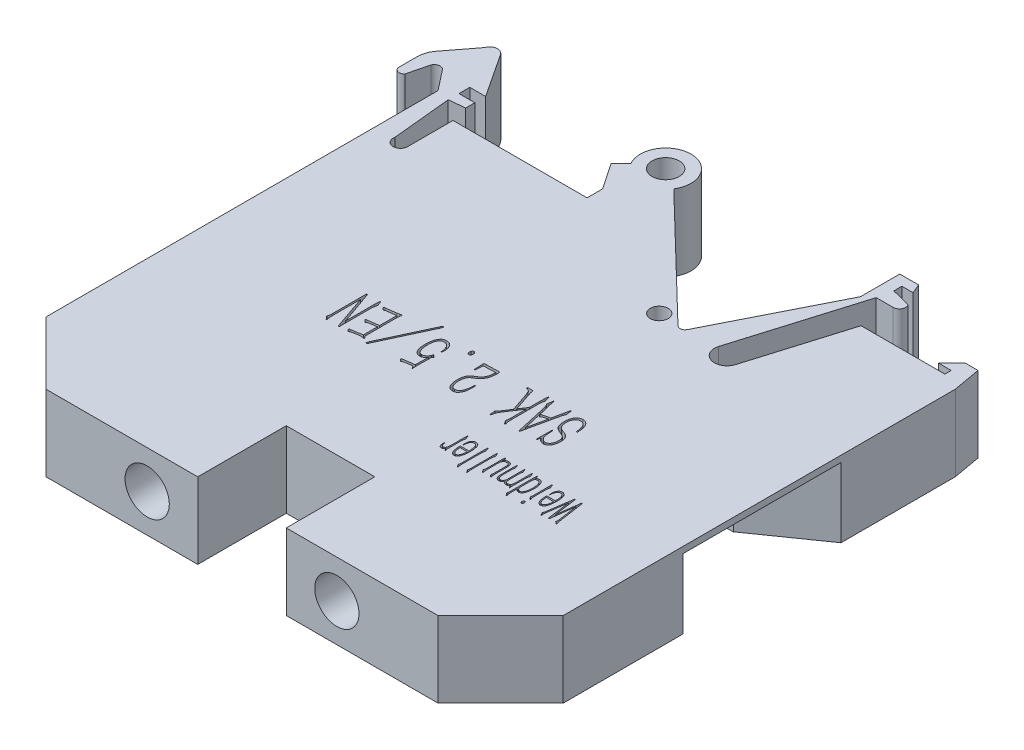
SolidWorks part; units mm, degrees
ref_plane "前视基准面" through (0, 0, 0) normal (0, 0, 1) x (1, 0, 0)
ref_plane "上视基准面" through (0, 0, 0) normal (0, 1, 0) x (1, 0, 0)
ref_plane "右视基准面" through (0, 0, 0) normal (1, 0, 0) x (0, 0, -1)
sketch "草图1" plane through (0, 0, 0) normal (0, 1, 0) x (1, 0, 0)
  line L0 (-61.5074, 0) -> (61.1732, 0) construction
  line L1 (0, 0) -> (0, 95.9382) construction
  line L2 (-3.5, 7) -> (3.5, 7)
  line L3 (3.5, 7) -> (3.5, 0)
  line L4 (3.5, 0) -> (15.5, 0)
  line L5 (15.5, 0) -> (20.4497, 4.9497)
  line L6 (20.4497, 4.9497) -> (20.4497, 35.9497)
  line L7 (-20.4497, 4.9497) -> (-20.4497, 35.9497)
  line L8 (-15.5, 0) -> (-20.4497, 4.9497)
  line L9 (-3.5, 0) -> (-15.5, 0)
  line L10 (-3.5, 7) -> (-3.5, 0)
  line L11 (20.4497, 35.9497) -> (20.0647, 38.1333)
  line L12 (20.0647, 38.1333) -> (19.0647, 38.1333)
  line L13 (19.0647, 38.1333) -> (18.0041, 37.0726)
  line L14 (18.0041, 37.0726) -> (19.0041, 37.0726)
  line L15 (19.0041, 37.0726) -> (19.0041, 36.5726)
  line L16 (-18.9543, 31.0334) -> (-19.4188, 35.7245)
  line L17 (12.3799, 36.5726) -> (10.0805, 28.9455)
  line L18 (8.1656, 29.5227) -> (11.052, 39.0971)
  line L19 (11.052, 39.0971) -> (12.3896, 39.0971)
  line L20 (12.8059, 39.874) -> (11.2867, 40.2529)
  line L21 (11.2867, 40.2529) -> (11.2867, 40.8921)
  line L22 (11.2867, 40.8921) -> (12.1702, 40.8921)
  line L23 (12.1702, 40.8921) -> (11.8608, 41.6446)
  line L24 (11.8608, 41.6446) -> (10.3682, 41.6446)
  line L25 (10.3682, 41.6446) -> (10.3682, 38.5389)
  line L26 (10.3682, 38.5389) -> (5.7821, 29.4476)
  line L27 (5.1289, 29.344) -> (-4.3994, 38.5389)
  line L28 (-7.833, 38.5907) -> (-8.6206, 37.803)
  line L29 (-8.6206, 37.803) -> (-7.2128, 35.7245)
  line L30 (-7.2128, 35.7245) -> (-7.2128, 34.4978)
  line L31 (-7.2128, 34.4978) -> (-17.8128, 34.4978)
  line L32 (-17.8128, 34.4978) -> (-17.8128, 30.9126)
  line L33 (-19.4188, 35.7245) -> (-18.1635, 35.8488)
  line L34 (12.3799, 36.5726) -> (-28.4316, 36.5726) construction
  line L35 (-18.1635, 35.8488) -> (-18.1635, 36.5726)
  line L36 (-18.1635, 36.5726) -> (-19.4188, 36.5726)
  line L37 (-19.4188, 36.5726) -> (-19.4188, 37.429)
  line L38 (-19.4188, 37.429) -> (-18.1635, 37.429)
  line L39 (-18.1635, 37.429) -> (-20.4497, 40.8921)
  line L40 (-21.5551, 40.7351) -> (-23.2038, 38.5907)
  line L41 (-23.5988, 37.429) -> (-23.5988, 35.9497)
  line L42 (-22.9, 35.7733) -> (-22.4849, 37.429)
  line L43 (-21.639, 37.4666) -> (-20.4497, 35.9497)
  line L45 (19.0041, 36.5726) -> (12.3799, 36.5726)
  arc A0 (10.0805, 28.9455) -> (8.1656, 29.5227) centre (9.123, 29.2341) cw
  arc A1 (12.3896, 39.0971) -> (12.8059, 39.874) centre (12.3896, 39.5971) ccw
  arc A2 (5.7821, 29.4476) -> (5.1289, 29.344) centre (5.4182, 29.6311) cw
  arc A3 (-4.3994, 38.5389) -> (-7.833, 38.5907) centre (-6.1005, 39.6013) ccw
  arc A4 (-17.8128, 30.9126) -> (-18.9543, 31.0334) centre (-18.3899, 30.9126) cw
  arc A5 (-20.4497, 40.8921) -> (-21.5551, 40.7351) centre (-20.9652, 40.5517) ccw
  arc A6 (-23.2038, 38.5907) -> (-23.5988, 37.429) centre (-21.6929, 37.429) ccw
  arc A7 (-23.5988, 35.9497) -> (-22.9, 35.7733) centre (-23.2038, 36.0421) ccw
  arc A8 (-22.4849, 37.429) -> (-21.639, 37.4666) centre (-22.0534, 37.2546) cw
  point P16 (0, 7)
  dimension "D8" = 0.5
  dimension "D9" = 0.5
  dimension "D1" = 7
  dimension "D2" = 7
  dimension "D3" = 12
  dimension "D4" = 7
  dimension "D5" = 135
  dimension "D6" = 31
  dimension "D7" = 10.6
  dimension "D10" = 1
  dimension "D11" = 1.5
  dimension "D12" = 1
extrude "凸台-拉伸1" add sketch "草图1" along normal blind 6
sketch "草图2" plane through (0, 0, 0) normal (0, 0, 1) x (1, 0, 0)
  line L0 (-3.5, 6) -> (-3.5, 0) construction
  line L1 (3.5, 6) -> (3.5, 0) construction
  circle A0 centre (-7.5, 3) radius 1.75
  circle A1 centre (7.5, 3) radius 1.75
  point P6 (-3.5, 3)
  point P7 (3.5, 3)
  dimension "D1" = 3.5
  dimension "D2" = 4
  dimension "D3" = 4
extrude "切除-拉伸1" cut sketch "草图2" against normal blind 5
sketch "草图3" plane through (0, 0, -5) normal (0, 0, 1) x (1, 0, 0)
  line L1 (-7.75, 1.5875) -> (-7.25, 1.5875)
  line L2 (-7.75, 1.5875) -> (-7.75, 4.4125)
  line L3 (-7.75, 4.4125) -> (-7.25, 4.4125)
  line L4 (-7.25, 1.5875) -> (-7.25, 4.4125)
  line L5 (-7.75, 1.5875) -> (-7.25, 4.4125) construction
  line L6 (-7.75, 4.4125) -> (-7.25, 1.5875) construction
  line L7 (7.25, 1.5875) -> (7.75, 1.5875)
  line L8 (7.25, 1.5875) -> (7.25, 4.4125)
  line L9 (7.25, 4.4125) -> (7.75, 4.4125)
  line L10 (7.75, 1.5875) -> (7.75, 4.4125)
  line L11 (7.25, 1.5875) -> (7.75, 4.4125) construction
  line L12 (7.25, 4.4125) -> (7.75, 1.5875) construction
  point P0 (-7.5, 3)
  point P6 (7.5, 3)
  dimension "D1" = 0.5
extrude "切除-拉伸2" cut sketch "草图3" against normal blind 1
sketch "草图4" plane through (0, 6, 0) normal (0, 1, 0) x (1, 0, 0)
  circle A0 centre (-6.1005, 39.6013) radius 1.0746
  arc A1 (-4.3994, 38.5389) -> (-7.833, 38.5907) centre (-6.1005, 39.6013) ccw construction
extrude "切除-拉伸3" cut sketch "草图4" against normal through all
sketch "草图5" plane through (0, 6, 0) normal (0, 1, 0) x (1, 0, 0)
  circle A0 centre (3.5586, 29.433) radius 0.7079
extrude "切除-拉伸4" cut sketch "草图5" against normal through all
sketch "草图6" plane through (-20.4497, 0, 0) normal (-1, 0, 0) x (0, 0, 1)
  line L0 (-35.9497, 0) -> (-4.9497, 0) construction
  line L1 (-26.9151, 5.5) -> (-14.4151, 5.5)
  line L2 (-26.9151, 5.5) -> (-26.9151, 0)
  line L3 (-26.9151, 0) -> (-14.4151, 0)
  line L4 (-14.4151, 5.5) -> (-14.4151, 0)
  line L5 (-26.9151, 5.5) -> (-14.4151, 0) construction
  line L6 (-26.9151, 0) -> (-14.4151, 5.5) construction
  point P0 (-20.6651, 2.75)
  dimension "D1" = 12.5
  dimension "D2" = 5.5
extrude "切除-拉伸5" cut sketch "草图6" against normal blind 5
sketch "草图7" plane through (0, 5.5, 0) normal (0, -1, 0) x (1, 0, 0)
  line L0 (-20.4497, -26.9151) -> (-15.4497, -26.9151)
  line L2 (-15.4497, -26.9151) -> (-15.4497, -23.4151)
  line L4 (-15.4497, -14.4151) -> (-15.4497, -26.9151) construction
  line L5 (-15.4497, -23.4151) -> (-20.4497, -26.9151)
  line L6 (-20.4497, -14.4151) -> (-15.4497, -14.4151)
  line L7 (-15.4497, -14.4151) -> (-15.4497, -17.9151)
  line L8 (-15.4497, -17.9151) -> (-20.4497, -14.4151)
  dimension "D1" = 3.5
  dimension "D2" = 3.5
extrude "凸台-拉伸2" add sketch "草图7" along normal up to surface (5.5 mm away) up to face at (-3.8878, 0, -30.6955)
sketch "草图8" plane through (-15.4497, 0, 0) normal (-1, 0, 0) x (0, 0, 1)
  line L0 (-17.9151, 0) -> (-17.9151, 5.5) construction
  line L1 (-23.3973, 0) -> (-17.9151, 0)
  line L2 (-23.3973, 0) -> (-23.3973, 4.6608)
  line L3 (-23.3973, 4.6608) -> (-17.9151, 4.6608)
  line L4 (-17.9151, 0) -> (-17.9151, 4.6608)
  line L5 (-23.3973, 0) -> (-17.9151, 4.6608) construction
  line L6 (-23.3973, 4.6608) -> (-17.9151, 0) construction
  point P0 (-20.6562, 2.3304)
extrude "切除-拉伸6" cut sketch "草图8" against normal blind 10
mirror "镜向1" about plane through (0, 0, 0) normal (1, 0, 0) of "切除-拉伸5", "凸台-拉伸2", "切除-拉伸6"
sketch "草图9" plane through (0, 6, 0) normal (0, 1, 0) x (1, 0, 0)
  line L0 (13.9859, 13.5861) -> (-4.0177, 13.5861) construction
  line L1 (9.6403, 19.4492) -> (-10.5878, 19.4492) construction
  text T0 "Weidmuller" font "汉仪长仿宋体" height in points 10
  text T1 "SAK 2.5/EN"
extrude "切除-拉伸7" cut sketch "草图9" against normal blind 1
sketch "草图10" plane through (5.4497, 0, 0) normal (1, 0, 0) x (0, 0, -1)
  line L0 (23.3973, 0) -> (17.9151, 0) construction
  line L1 (23.3973, 4.6608) -> (23.3973, 0) construction
  point P0 (20.6562, 2.3304)
  point P3 (20.6562, 0)
  point P6 (23.3973, 2.3304)
sketch "0_1_Point" plane through (-5.4497, 0, 0) normal (-1, 0, 0) x (0, 0, 1)
  point P0 (-20.6562, 2.3304)
sketch "0_0_Point" plane through (5.4497, 0, 0) normal (1, 0, 0) x (0, 0, -1)
  point P0 (20.6562, 2.3304)
other "0_0" parameters "直径"=2, "端头长度"=2
ref_axis "基准轴1" through (15.4497, 2.3304, -20.6562) along (-1, 0, 0)
other "0_1" parameters "直径"=2, "端头长度"=2
ref_axis "基准轴2" through (-15.4497, 2.3304, -20.6562) along (1, 0, 0)
